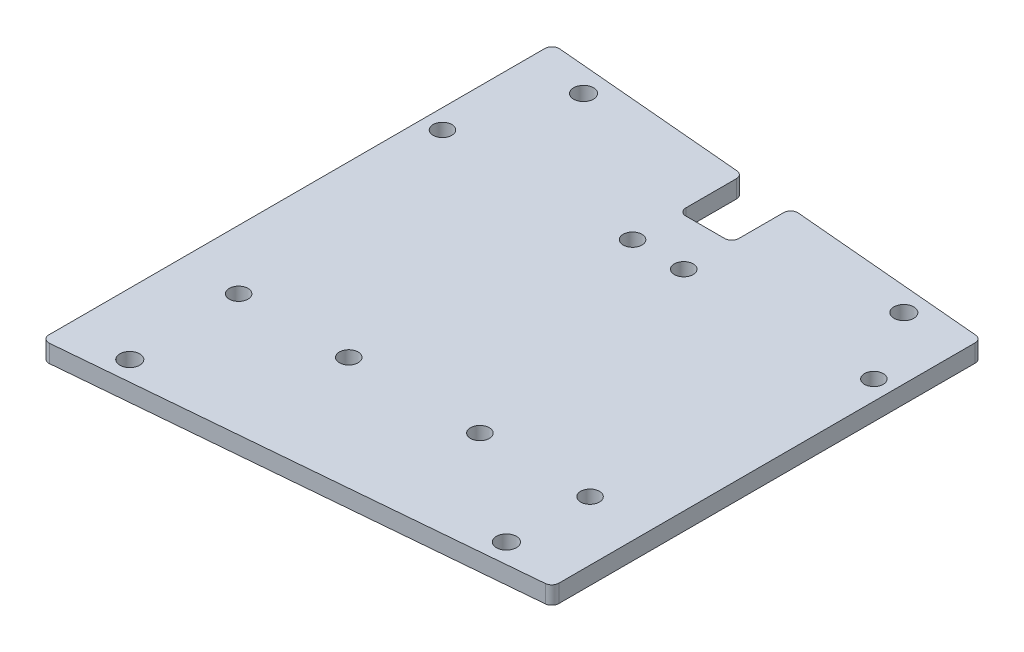
SolidWorks part; units mm, degrees
ref_plane "Front Plane" through (0, 0, 0) normal (0, 0, 1) x (1, 0, 0)
ref_plane "Top Plane" through (0, 0, 0) normal (0, 1, 0) x (1, 0, 0)
ref_plane "Right Plane" through (0, 0, 0) normal (1, 0, 0) x (0, 0, -1)
sketch "Sketch1" plane through (0, 0, 0) normal (0, 1, 0) x (1, 0, 0)
  line L0 (0, -76.835) -> (0, 76.835)
  line L1 (0, 76.835) -> (-175.26, 92.1683)
  line L2 (-175.26, 92.1683) -> (-175.26, -92.1683)
  line L3 (0, 0) -> (-175.26, 0) construction
  line L4 (0, -76.835) -> (-175.26, -92.1683)
  dimension "D1" = 175.26
  dimension "D2" = 95
  dimension "D3" = 76.835
extrude "Boss-Extrude1" add sketch "Sketch1" along normal blind 6.35
ref_plane "Plane1" through (-87.63, 0, 0) normal (1, 0, 0) x (0, 0, -1)
sketch "Sketch2" plane through (0, 6.35, 0) normal (0, 1, 0) x (1, 0, 0)
  line L0 (0, 76.835) -> (-175.26, 92.1683) construction
  line L1 (-78.105, 62.2766) -> (-97.155, 62.2766)
  line L2 (-78.105, 62.2766) -> (-78.105, 106.7266)
  line L3 (-78.105, 106.7266) -> (-97.155, 106.7266)
  line L4 (-97.155, 62.2766) -> (-97.155, 106.7266)
  line L5 (-78.105, 62.2766) -> (-97.155, 106.7266) construction
  line L6 (-78.105, 106.7266) -> (-97.155, 62.2766) construction
  point P0 (-87.63, 84.5016)
  dimension "D1" = 19.05
  dimension "D2" = 44.45
extrude "Cut-Extrude1" cut sketch "Sketch2" against normal through all
hole_wizard "17/64 (0.26563) Diameter Hole1" positions "Sketch3" profile "Sketch4" hole size "17/64" standard "ANSI Inch" end condition through all
sketch "Sketch3" plane through (0, 6.35, 0) normal (0, 1, 0) x (1, 0, 0)
  point P0 (-24.485, -42.27)
  point P3 (-64.0721, -42.27)
  point P6 (-111.1879, -42.27)
  point P9 (-150.775, -42.27)
  point P12 (-78.4321, 45.355)
  point P15 (-10.125, 45.355)
  point P18 (-96.8279, 45.355)
  point P21 (-165.135, 45.355)
sketch "Sketch4" plane through (-24.485, 6.35, 42.27) normal (1, 0, 0) x (0, 0, 1)
  line L0 (0, 0) -> (0, 6.35)
  line L1 (0, 6.35) -> (3.3735, 6.35)
  line L2 (3.3735, 6.35) -> (3.3735, 0)
  line L5 (3.3735, 0) -> (0, 0)
  line L11 (0, -6.35) -> (0, 107.95) construction
  dimension "Thru Hole Dia." = 6.747
  dimension "Thru Hole Depth" = 6.35
hole_wizard "1/4 Clearance Hole1" positions "Sketch5" profile "Sketch6" hole size "1/4" standard "ANSI Inch" end condition through all
sketch "Sketch5" plane through (0, 6.35, 0) normal (0, 1, 0) x (1, 0, 0)
  line L0 (-201.93, 12.7) -> (-1192.53, 12.7) construction
  circle A0 centre (-25.4, 71.4004) radius 3.3782 construction
  circle A1 centre (-25.4, -71.4004) radius 3.3782 construction
  circle A2 centre (-149.86, -82.2892) radius 3.3782 construction
  point P0 (-25.4, 71.4004)
  point P2 (-25.4, -71.4004)
  point P4 (-149.86, -82.2892)
  point P6 (-151.13, 82.042)
  dimension "D1" = 1.27
  dimension "D2" = 69.342
sketch "Sketch6" plane through (-25.4, 6.35, -71.4004) normal (1, 0, 0) x (0, 0, 1)
  line L0 (0, 0) -> (0, 6.35)
  line L1 (0, 6.35) -> (3.5712, 6.35)
  line L2 (3.5712, 6.35) -> (3.5712, 0)
  line L5 (3.5712, 0) -> (0, 0)
  line L11 (0, -6.35) -> (0, 107.95) construction
  dimension "Thru Hole Dia." = 7.1425
  dimension "Thru Hole Depth" = 6.35
sketch "Sketch7" plane through (0, 6.35, 0) normal (0, 1, 0) x (1, 0, 0)
  line L0 (0, 76.835) -> (-78.105, 83.6683) construction
  line L1 (-175.26, 92.1683) -> (-172.085, 92.1683)
  line L2 (-175.26, 92.1683) -> (-175.26, -92.1683)
  line L3 (-175.26, -92.1683) -> (-172.085, -92.1683)
  line L4 (-172.085, 92.1683) -> (-172.085, -92.1683)
  line L5 (-3.175, 77.1128) -> (0, 77.1128)
  line L6 (-3.175, 77.1128) -> (-3.175, -77.1128)
  line L7 (-3.175, -77.1128) -> (0, -77.1128)
  line L8 (0, 77.1128) -> (0, -77.1128)
  line L9 (-175.26, -92.1683) -> (0, -76.835) construction
  dimension "D1" = 3.175
extrude "Cut-Extrude2" cut sketch "Sketch7" against normal through all
fillet "Fillet1" radius 2.54 8 edges at (-97.155, 3.175, -85.335) (-78.105, 3.175, -83.6683) (-78.105, 3.175, -62.2766) (-97.155, 3.175, -62.2766) (-3.175, 3.175, -77.1128) (-3.175, 3.175, 77.1128) (-172.085, 3.175, 91.8905) (-172.085, 3.175, -91.8905)
